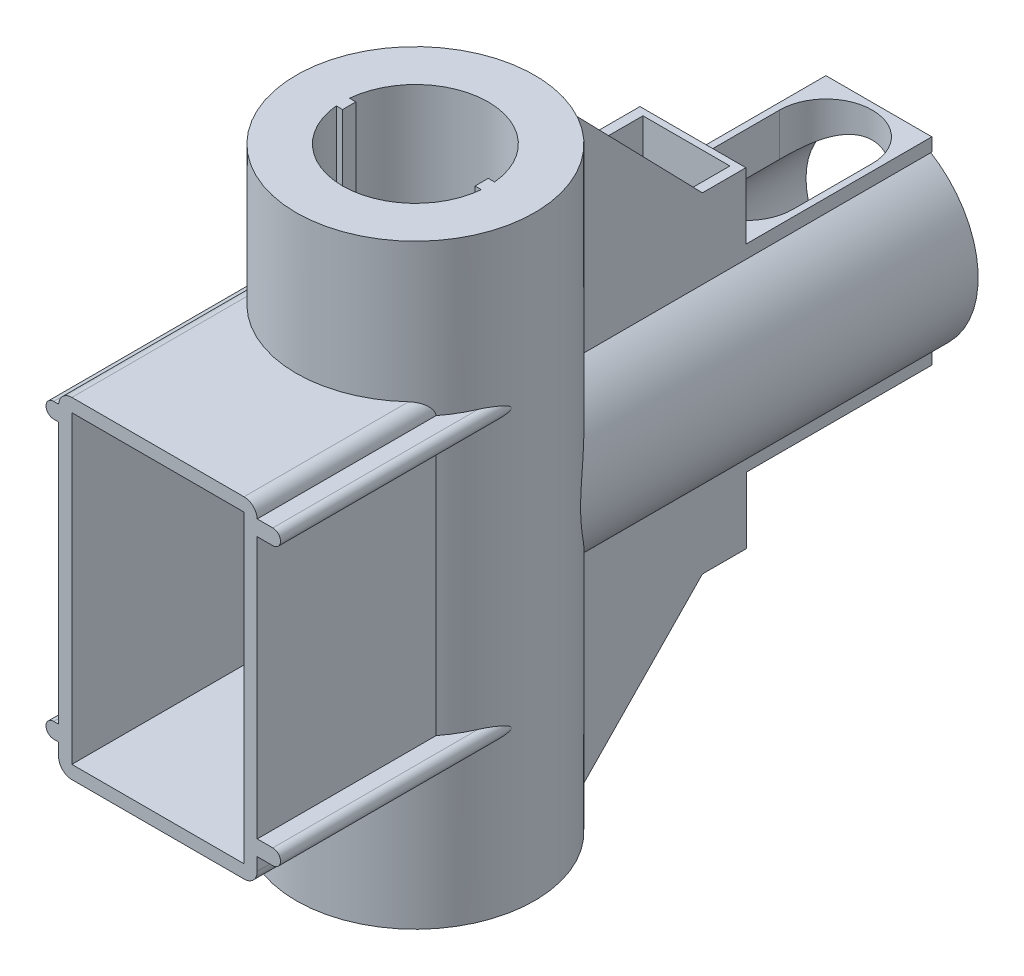
SolidWorks part; units mm, degrees
material "PET"
ref_plane "Front Plane" through (0, 0, 0) normal (0, 0, 1) x (1, 0, 0)
ref_plane "Top Plane" through (0, 0, 0) normal (0, 1, 0) x (1, 0, 0)
ref_plane "Right Plane" through (0, 0, 0) normal (1, 0, 0) x (0, 0, -1)
sketch "Sketch1" plane through (0, 0, 0) normal (0, 0, 1) x (1, 0, 0)
  circle A0 centre (0, 0) radius 7.5
  dimension "D1" = 15
extrude "Boss-Extrude1" add sketch "Sketch1" along normal blind 33
sketch "Sketch2" plane through (0, 0, 0) normal (0, 0, -1) x (-1, 0, 0)
  circle A0 centre (0, 0) radius 5.5
extrude "Cut-Extrude1" cut sketch "Sketch2" against normal blind 25
sketch "Sketch4" plane through (0, 0, 0) normal (0, 1, 0) x (1, 0, 0)
  line L0 (0, -10) -> (0, -4) construction
  line L1 (-3.5, -10) -> (-3.5, -4)
  line L2 (3.5, -10) -> (3.5, -4)
  arc A0 (-3.5, -10) -> (3.5, -10) centre (0, -10) ccw
  arc A1 (3.5, -4) -> (-3.5, -4) centre (0, -4) ccw
  point P2 (0, -7)
  dimension "D1" = 7
sketch "Sketch9" plane through (0, 0, 0) normal (0, 1, 0) x (1, 0, 0)
  circle A0 centre (0, -35) radius 9
  dimension "D1" = 18
extrude "Boss-Extrude9" add sketch "Sketch9" along normal blind 22.5 and the other way blind 22.5 separate body
sketch "Sketch10" plane through (0, 22.5, 0) normal (0, 1, 0) x (1, 0, 0)
  circle A0 centre (0, -35) radius 5.5
  dimension "D1" = 11
ref_plane "Plane1" through (0, 0, 54.0419) normal (0, 0, 1) x (1, 0, 0)
sketch "Sketch11" plane through (0, 0, 54.0419) normal (0, 0, 1) x (1, 0, 0)
  line L1 (-6.9019, 11.9933) -> (6.0981, 11.9933)
  line L2 (-7.9019, 10.9933) -> (-7.9019, -12.0067)
  line L3 (-6.9019, -13.0067) -> (6.0981, -13.0067)
  line L4 (7.0981, 10.9933) -> (7.0981, -12.0067)
  arc A0 (-7.9019, -12.0067) -> (-6.9019, -13.0067) centre (-6.9019, -12.0067) ccw
  arc A1 (6.0981, -13.0067) -> (7.0981, -12.0067) centre (6.0981, -12.0067) ccw
  arc A2 (6.0981, 11.9933) -> (7.0981, 10.9933) centre (6.0981, 10.9933) cw
  arc A3 (-6.9019, 11.9933) -> (-7.9019, 10.9933) centre (-6.9019, 10.9933) ccw
  dimension "D1" = 1
  dimension "D2" = 23
  dimension "D3" = 13
extrude "Boss-Extrude10" add sketch "Sketch11" against normal blind 17.5
sketch "Sketch12" plane through (0, 0, 54.0419) normal (0, 0, 1) x (1, 0, 0)
  line L0 (7.0981, 10.4634) -> (8.2734, 10.4634) construction
  line L1 (7.0981, -12.0067) -> (7.0981, 10.9933) construction
  line L2 (7.0981, 11.0452) -> (8.2734, 11.0452)
  line L3 (7.0981, 9.8817) -> (8.2734, 9.8817)
  arc A0 (7.0981, 11.0452) -> (7.0981, 9.8817) centre (7.0981, 10.4634) ccw
  arc A1 (8.2734, 9.8817) -> (8.2734, 11.0452) centre (8.2734, 10.4634) ccw
  point P4 (7.6857, 10.4634)
extrude "Boss-Extrude11" add sketch "Sketch12" against normal blind 17.5
sketch "Sketch16" plane through (0, 0, 0) normal (0, 0, 1) x (1, 0, 0)
  line L1 (4, 12.4668) -> (-4, 12.4668)
  line L2 (4, 12.4668) -> (4, 6.4668)
  line L3 (4, 6.4668) -> (-4, 6.4668)
  line L4 (-4, 12.4668) -> (-4, 6.4668)
  line L5 (4, 12.4668) -> (-4, 6.4668) construction
  line L6 (4, 6.4668) -> (-4, 12.4668) construction
  point P0 (0, 9.4668)
  dimension "D1" = 6
  dimension "D2" = 8
extrude "Boss-Extrude12" add sketch "Sketch16" along normal blind 29.5
sketch "Sketch20" plane through (0, 0, 0) normal (1, 0, 0) x (0, 0, -1)
  line L0 (-27.0909, 22.5) -> (-26.9377, 12.4668)
  line L1 (-26, 22.5) -> (-44, 22.5) construction
  line L2 (-26.9377, 12.4668) -> (-17.327, 12.4668)
  line L3 (-26.9377, 12.4668) -> (0, 12.4668) construction
  line L4 (-17.327, 12.4668) -> (-27.0909, 22.5)
  dimension "D1" = 14
extrude "Boss-Extrude13" add sketch "Sketch20" along normal blind 4 and the other way blind 4
mirror "Mirror9" about plane through (0, 0, 0) normal (0, 1, 0) of "Boss-Extrude13", "Boss-Extrude12"
mirror "Mirror10" about plane through (0, 0, 0) normal (0, 1, 0) of "Boss-Extrude11"
mirror "Mirror11" about plane through (0, 0, 0) normal (1, 0, 0) of "Mirror10"
extrude "Cut-Extrude4" cut sketch "Sketch4" against normal blind 14 and the other way blind 15
extrude "Cut-Extrude5" cut sketch "Sketch10" against normal blind 50 contours A0
sketch "Sketch22" plane through (0, 0, 54.0419) normal (0, 0, 1) x (1, 0, 0)
  line L1 (-6.9019, 10.9933) -> (6.0981, 10.9933)
  line L2 (-6.9019, 10.9933) -> (-6.9019, -12.0067)
  line L3 (-6.9019, -12.0067) -> (6.0981, -12.0067)
  line L4 (6.0981, 10.9933) -> (6.0981, -12.0067)
extrude "Cut-Extrude6" cut sketch "Sketch22" against normal blind 18
sketch "Sketch23" plane through (0, 0, 0) normal (0, 1, 0) x (1, 0, 0)
  line L1 (-3.2828, -14.5341) -> (3.2828, -14.5341)
  line L2 (-3.2828, -14.5341) -> (-3.2828, -25.3414)
  line L3 (-3.2828, -25.3414) -> (3.2828, -25.3414)
  line L4 (3.2828, -14.5341) -> (3.2828, -25.3414)
  line L5 (-3.2828, -14.5341) -> (3.2828, -25.3414) construction
  line L6 (-3.2828, -25.3414) -> (3.2828, -14.5341) construction
  point P0 (0, -19.9377)
extrude "Cut-Extrude7" cut sketch "Sketch23" against normal blind 29 and the other way blind 42
sketch "Sketch24" plane through (0, 0, 0) normal (0, 1, 0) x (1, 0, 0)
  line L0 (-7.5, 0) -> (-7.5, -33) construction
  line L1 (-7.5, -13.1024) -> (-15.5, -13.1024)
  line L2 (-7.5, -13.1024) -> (-7.5, -6.1024)
  line L3 (-7.5, -6.1024) -> (-15.5, -6.1024)
  line L4 (-16.5, -12.1024) -> (-16.5, -7.1024)
  arc A0 (-15.5, -13.1024) -> (-16.5, -12.1024) centre (-15.5, -12.1024) cw
  arc A1 (-15.5, -6.1024) -> (-16.5, -7.1024) centre (-15.5, -7.1024) ccw
  point P8 (-16.5, -13.1024)
  point P11 (-16.5, -6.1024)
  dimension "D3" = 1
  dimension "D1" = 7
  dimension "D2" = 9
extrude "Boss-Extrude14" add sketch "Sketch24" along normal blind 1 and the other way blind 1
ref_plane "Plane6" through (0, 0, 10) normal (0, 0, 1) x (1, 0, 0)
sketch "Sketch26" plane through (0, 12.4668, 0) normal (0, 1, 0) x (1, 0, 0)
  line L0 (4, -17.327) -> (4, 0) construction
  line L1 (-4, 0.0436) -> (4, 0.0436)
  line L2 (-4, 0.0436) -> (-4, -14.0436)
  line L3 (-4, -14.0436) -> (4, -14.0436)
  line L4 (4, 0.0436) -> (4, -14.0436)
  line L5 (-4, 0.0436) -> (4, -14.0436) construction
  line L6 (-4, -14.0436) -> (4, 0.0436) construction
  point P0 (0, -7)
extrude "Cut-Extrude8" cut sketch "Sketch26" against normal blind 5
sketch "Sketch27" plane through (0, -12.4668, 0) normal (0, -1, 0) x (1, 0, 0)
  line L1 (-4, 14) -> (4, 14)
  line L2 (-4, 14) -> (-4, 0)
  line L3 (-4, 0) -> (4, 0)
  line L4 (4, 14) -> (4, 0)
  line L5 (-4, 14) -> (4, 0) construction
  line L6 (-4, 0) -> (4, 14) construction
  point P0 (0, 7)
extrude "Cut-Extrude9" cut sketch "Sketch27" against normal blind 5
sketch "Sketch29" plane through (0, -22.5, 0) normal (0, -1, 0) x (1, 0, 0)
  line L1 (-6, 35.5) -> (-5, 35.5)
  line L2 (-6, 35.5) -> (-6, 34.5)
  line L3 (-6, 34.5) -> (-5, 34.5)
  line L4 (-5, 35.5) -> (-5, 34.5)
  line L5 (-6, 35.5) -> (-5, 34.5) construction
  line L6 (-6, 34.5) -> (-5, 35.5) construction
  line L7 (5, 35.5) -> (6, 35.5)
  line L8 (5, 35.5) -> (5, 34.5)
  line L9 (5, 34.5) -> (6, 34.5)
  line L10 (6, 35.5) -> (6, 34.5)
  line L11 (5, 35.5) -> (6, 34.5) construction
  line L12 (5, 34.5) -> (6, 35.5) construction
  circle A0 centre (0, 35) radius 5.5 construction
  circle A1 centre (0, 35) radius 5.5 construction
  point P0 (-5.5, 35)
  point P7 (5.5, 35)
  dimension "D1" = 1
  dimension "D2" = 1
  dimension "D3" = 1
extrude "Boss-Extrude15" add sketch "Sketch29" against normal blind 45
